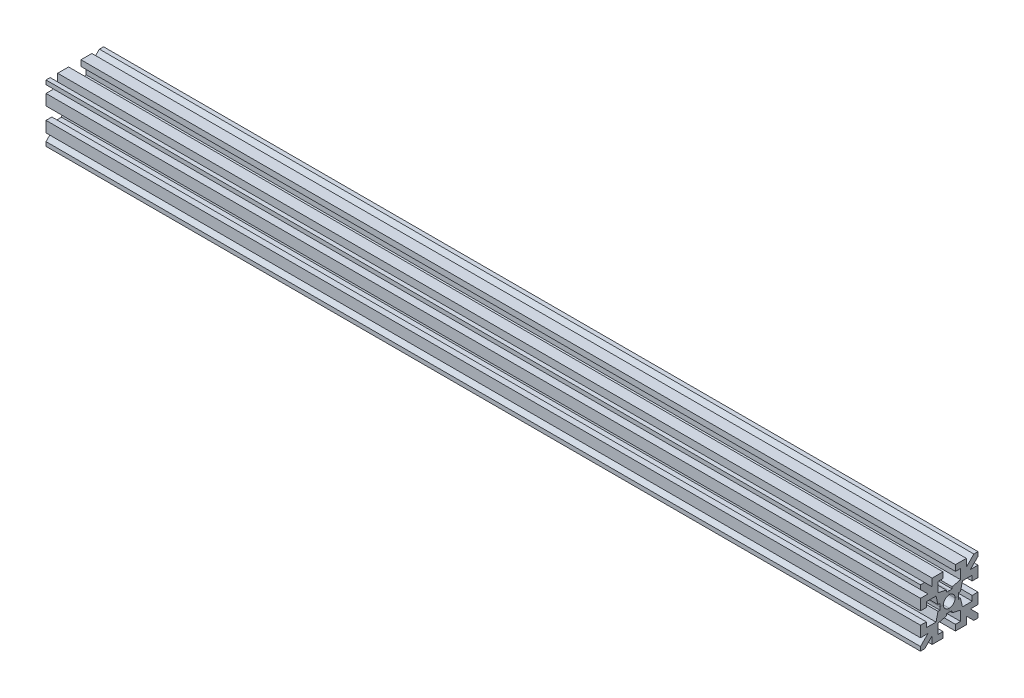
SolidWorks part; units mm, degrees
material "6061 Alloy"
ref_plane "Front Plane" through (0, 0, 0) normal (0, 0, 1) x (1, 0, 0)
ref_plane "Top Plane" through (0, 0, 0) normal (0, 1, 0) x (1, 0, 0)
ref_plane "Right Plane" through (0, 0, 0) normal (1, 0, 0) x (0, 0, -1)
sketch "Sketch1" plane through (0, 0, 0) normal (1, 0, 0) x (0, 0, -1)
  line L0 (-2.4, 0) -> (-2.4, 0.75)
  line L1 (-2.4, 0.75) -> (-2.9, 0.75)
  line L2 (-2.9, 0.75) -> (-3.4, 2.9)
  line L3 (55, 0) -> (-55, 0) construction
  line L4 (0, 2.4) -> (-0.75, 2.4)
  line L5 (-0.75, 2.4) -> (-0.75, 2.9)
  line L6 (-0.75, 2.9) -> (-2.9, 3.4)
  line L7 (-3.4, 2.9) -> (-5.9, 2.9)
  line L8 (-5.9, 2.9) -> (-5.9, 1.6)
  line L9 (-5.9, 1.6) -> (-7.4, 1.6)
  line L10 (-7.4, 1.6) -> (-7.4, 4.4)
  line L11 (-7.4, 4.4) -> (-5.4607, 4.4)
  line L12 (-5.4607, 4.4) -> (-7.4, 6.3393)
  line L13 (-7.4, 6.3393) -> (-7.4, 7.4)
  line L14 (-7.4, 7.4) -> (-6.3393, 7.4)
  line L15 (-6.3393, 7.4) -> (-4.4, 5.4607)
  line L16 (-4.4, 5.4607) -> (-4.4, 7.4)
  line L17 (-4.4, 7.4) -> (-1.6, 7.4)
  line L18 (-1.6, 7.4) -> (-1.6, 5.9)
  line L19 (-1.6, 5.9) -> (-2.9, 5.9)
  line L20 (-2.9, 5.9) -> (-2.9, 3.4)
  line L24 (0, 55) -> (0, -55) construction
  line L25 (-1.5, 0) -> (-2.4, 0)
  line L26 (0, 1.5) -> (0, 2.4)
  line L27 (0, 0) -> (-29.7367, 29.7367) construction
  arc A0 (-1.5, 0) -> (0, 1.5) centre (0, 0) cw
  dimension "D5" = 1.5
  dimension "D1" = 45
  dimension "D2" = 1.5
  dimension "D3" = 1.5
  dimension "D4" = 4.5
  dimension "D6" = 7.4
  dimension "D7" = 5.8
  dimension "D8" = 3
  dimension "D9" = 2.5
  dimension "D10" = 0.75
  dimension "D11" = 0.5
  dimension "D12" = 2.4
extrude "Boss-Extrude1" add sketch "Sketch1" against normal blind 225
ref_axis "Axis1" through (-262.5, 0, 0) along (1, 0, 0)
pattern_circular "CirPattern1" count 4 every 90 about axis through (-262.5, 0, 0) along (1, 0, 0) of bodies 106
